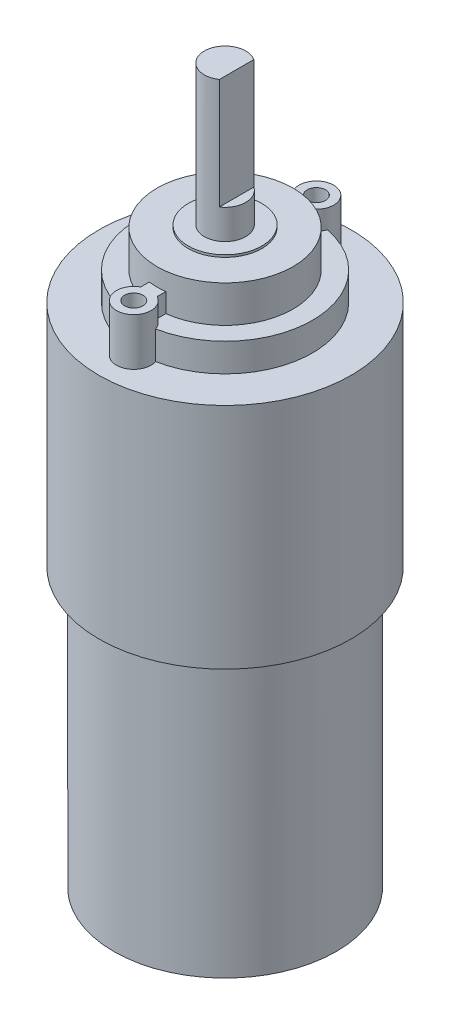
SolidWorks part; units mm, degrees
ref_plane "Front Plane" through (0, 0, 0) normal (0, 0, 1) x (1, 0, 0)
ref_plane "Top Plane" through (0, 0, 0) normal (0, 1, 0) x (1, 0, 0)
ref_plane "Right Plane" through (0, 0, 0) normal (1, 0, 0) x (0, 0, -1)
sketch "Front cylinder sketch" plane through (0, 0, 0) normal (0, 1, 0) x (1, 0, 0)
  circle A0 centre (10.0709, -22.416) radius 13.7
  dimension "D1" = 27.4
extrude "Front Cylinder" add sketch "Front cylinder sketch" along normal blind 24.8127
sketch "Mounting Point Sketch" plane through (0, 24.8127, 0) normal (0, 1, 0) x (1, 0, 0)
  line L0 (10.0709, -8.716) -> (10.0709, -36.116) construction
  line L1 (-3.6291, -22.416) -> (23.7709, -22.416) construction
  line L2 (9.1709, -14.1485) -> (9.1709, -15.0798)
  line L3 (10.9709, -14.1485) -> (10.9709, -15.0798)
  line L4 (10.9709, -30.6834) -> (10.9709, -29.7521)
  line L5 (9.1709, -30.6834) -> (9.1709, -29.7521)
  circle A0 centre (10.0709, -22.416) radius 13.7 construction
  circle A1 centre (10.0709, -12.496) radius 1
  circle A2 centre (10.0709, -32.336) radius 1
  circle A3 centre (10.0709, -12.496) radius 1.8817
  circle A4 centre (10.0709, -32.336) radius 1.8817
  circle A5 centre (10.0709, -22.416) radius 7.3911 construction
  arc A6 (9.1709, -15.0798) -> (10.9709, -15.0798) centre (10.0709, -22.416) cw
  arc A7 (9.1709, -29.7521) -> (10.9709, -29.7521) centre (10.0709, -22.416) ccw
  dimension "D1" = 2
  dimension "D2" = 19.84
  dimension "D3" = 1.8
extrude "Mounting Points" add sketch "Mounting Point Sketch" along normal blind 5.15 contours A3 A1 | L2 A6 L3 A3 | A4 A2 | A7 L5 A4 L4 region at (10.0709, 24.8127, 14.6703) region at (9.137, 24.8127, 10.9239) region at (10.0709, 24.8127, 30.1617) region at (11.643, 24.8127, 31.4021)
sketch "Gear Mount Bottom Sketch" plane through (0, 24.8127, 0) normal (0, 1, 0) x (1, 0, 0)
  circle A0 centre (10.0709, -22.416) radius 9.5
  dimension "D1" = 19
extrude "Gear Mount Bottom" add sketch "Gear Mount Bottom Sketch" along normal blind 3.0747
sketch "Gear Mount Top Sketch" plane through (0, 27.8874, 0) normal (0, 1, 0) x (1, 0, 0)
  line L4 (10.9709, -14.1485) -> (10.9709, -15.0798)
  line L5 (9.1709, -15.0798) -> (9.1709, -14.1485)
  line L6 (9.1709, -30.6834) -> (9.1709, -29.7521)
  line L7 (10.9709, -29.7521) -> (10.9709, -30.6834)
  line L8 (10.9709, -14.1485) -> (10.9709, -15.0798)
  line L9 (9.1709, -15.0798) -> (9.1709, -14.1485)
  line L10 (9.1709, -30.6834) -> (9.1709, -29.7521)
  line L11 (10.9709, -29.7521) -> (10.9709, -30.6834)
  circle A0 centre (10.0709, -22.416) radius 7.3911
  arc A8 (10.9709, -14.1485) -> (11.8579, -13.0856) centre (10.0709, -12.496) ccw
  arc A9 (10.9709, -15.0798) -> (9.1709, -15.0798) centre (10.0709, -22.416) ccw
  arc A10 (8.284, -13.0856) -> (9.1709, -14.1485) centre (10.0709, -12.496) ccw
  arc A11 (8.284, -13.0856) -> (8.284, -31.7464) centre (10.0709, -22.416) ccw
  arc A12 (9.1709, -30.6834) -> (8.284, -31.7464) centre (10.0709, -32.336) ccw
  arc A13 (9.1709, -29.7521) -> (10.9709, -29.7521) centre (10.0709, -22.416) ccw
  arc A14 (11.8579, -31.7464) -> (10.9709, -30.6834) centre (10.0709, -32.336) ccw
  arc A15 (11.8579, -31.7464) -> (11.8579, -13.0856) centre (10.0709, -22.416) ccw
  arc A16 (10.9709, -14.1485) -> (11.8579, -13.0856) centre (10.0709, -12.496) ccw
  arc A17 (10.9709, -15.0798) -> (9.1709, -15.0798) centre (10.0709, -22.416) ccw
  arc A18 (8.284, -13.0856) -> (9.1709, -14.1485) centre (10.0709, -12.496) ccw
  arc A19 (8.284, -13.0856) -> (8.284, -31.7464) centre (10.0709, -22.416) ccw
  arc A20 (9.1709, -30.6834) -> (8.284, -31.7464) centre (10.0709, -32.336) ccw
  arc A21 (9.1709, -29.7521) -> (10.9709, -29.7521) centre (10.0709, -22.416) ccw
  arc A22 (11.8579, -31.7464) -> (10.9709, -30.6834) centre (10.0709, -32.336) ccw
  arc A23 (11.8579, -31.7464) -> (11.8579, -13.0856) centre (10.0709, -22.416) ccw
  arc M15 (10.9709, -15.0798) -> (9.1709, -15.0798) centre (10.0709, -22.416) ccw
  arc M21 (9.1709, -29.7521) -> (10.9709, -29.7521) centre (10.0709, -22.416) ccw
  dimension "D1" = 0
extrude "Gear Mount Top" add sketch "Gear Mount Top Sketch" along normal blind 4 contours A0 M21 M15 region at (10.0709, 27.8874, 22.416)
sketch "Mounting Holes Sketch" plane through (0, 24.8127, 0) normal (0, 1, 0) x (1, 0, 0)
  circle A0 centre (10.0709, -12.496) radius 1
  circle A1 centre (10.0709, -32.336) radius 1
extrude "Mounting Holes" cut sketch "Mounting Holes Sketch" along normal up to next
sketch "Gear Disk Sketch" plane through (0, 31.8874, 0) normal (0, 1, 0) x (1, 0, 0)
  circle A0 centre (10.0709, -22.416) radius 4
  circle A1 centre (10.0709, -22.416) radius 7.3911
  circle A2 centre (10.0709, -22.416) radius 7.3911
  dimension "D2" = 8
  dimension "D1" = 0
extrude "Gear disk" add sketch "Gear Disk Sketch" along normal blind 0.25 contours A0
sketch "Gear Sketch" plane through (0, 32.1374, 0) normal (0, 1, 0) x (1, 0, 0)
  circle A0 centre (10.0709, -22.416) radius 2.25
  circle A1 centre (10.0709, -22.416) radius 4
  circle A2 centre (10.0709, -22.416) radius 4
  dimension "D2" = 4.5
  dimension "D1" = 0
extrude "Gear" add sketch "Gear Sketch" along normal blind 15.225 contours A0
sketch "Gear Notch Sketch" plane through (0, 47.3624, 0) normal (0, 1, 0) x (1, 0, 0)
  line L0 (11.3209, -20.5451) -> (11.3209, -24.2868)
  arc A0 (11.3209, -20.5451) -> (11.3209, -24.2868) centre (10.0709, -22.416) cw
  circle A1 centre (10.0709, -22.416) radius 2.25
  circle A2 centre (10.0709, -22.416) radius 2.25
  circle M3 centre (10.0709, -22.416) radius 2.25
  dimension "D2" = 1.25
  dimension "D1" = 0
extrude "Gear Notch" cut sketch "Gear Notch Sketch" against normal blind 12 contours L0 M3 region at (11.7297, 47.3624, 22.416)
sketch "Back Cylinder Sketch" plane through (0, 0, 0) normal (0, -1, 0) x (1, 0, 0)
  circle A0 centre (10.0709, 22.416) radius 12.1
  circle A1 centre (10.0709, 22.416) radius 13.7
  circle A2 centre (10.0709, 22.416) radius 13.7
  dimension "D2" = 24.2
  dimension "D1" = 0
extrude "Boss-Extrude7" add sketch "Back Cylinder Sketch" along normal blind 30.2 contours A0
